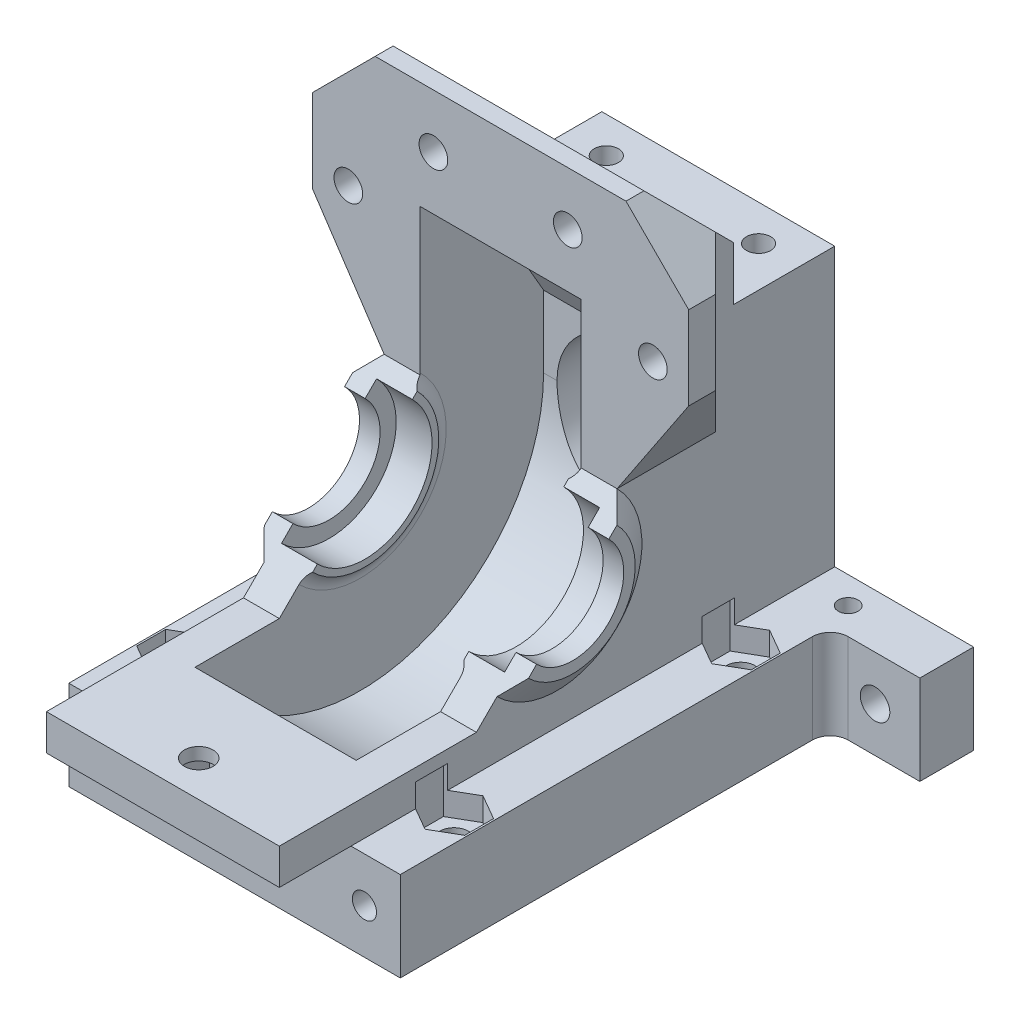
SolidWorks part; units mm, degrees
ref_plane "Plan de face" through (0, 0, 0) normal (0, 0, 1) x (1, 0, 0)
ref_plane "Plan de dessus" through (0, 0, 0) normal (0, 1, 0) x (1, 0, 0)
ref_plane "Plan de droite" through (0, 0, 0) normal (1, 0, 0) x (0, 0, -1)
ref_plane "Plan1" through (0, -23, 0) normal (0, 1, 0) x (1, 0, 0)
sketch "Esquisse1" plane through (0, -23, 0) normal (0, 1, 0) x (1, 0, 0)
  line L0 (0, 36.285) -> (0, -30.3608) construction
  line L1 (18.5, -23) -> (-18.5, -23)
  line L2 (-18.5, -23) -> (-18.5, 25)
  line L3 (-18.5, 25) -> (-28.5, 25)
  line L4 (-28.5, 25) -> (-28.5, 31)
  line L5 (-28.5, 31) -> (28.5, 31)
  line L6 (28.5, 25) -> (28.5, 31)
  line L7 (18.5, 25) -> (28.5, 25)
  line L8 (18.5, -23) -> (18.5, 25)
  circle A0 centre (-17.5, 28) radius 1.1
  circle A1 centre (-15.5, 18) radius 1.6
  circle A2 centre (-15.5, -14) radius 1.6
  circle A3 centre (15.5, -14) radius 1.6
  circle A4 centre (15.5, 18) radius 1.6
  circle A5 centre (17.5, 28) radius 1.1
  point P15 (-28.5, 28)
  point P23 (0, 31)
  point P26 (0, -23)
  dimension "D1" = 3.2
  dimension "D2" = 2.2
  dimension "D3" = 54
  dimension "D4" = 37
  dimension "D5" = 57
  dimension "D6" = 6
  dimension "D7" = 23
  dimension "D8" = 32
  dimension "D9" = 9
  dimension "D10" = 15.5
  dimension "D11" = 17.5
extrude "Boss.-Extru.1" add sketch "Esquisse1" along normal blind 10
sketch "Esquisse2" plane through (0, 0, 0) normal (1, 0, 0) x (0, 0, -1)
  line L0 (31, -13) -> (-31, -13)
  line L1 (-31, -13) -> (-31, -9)
  line L2 (-31, -9) -> (-9, -9)
  line L3 (-9, -9) -> (-4.0305, -4.0305)
  line L4 (6.7, 6.7) -> (6.7, 35)
  line L5 (6.7, 35) -> (8.7, 35)
  line L6 (8.7, 35) -> (19.7, 24)
  line L7 (19.7, 24) -> (19.7, 18)
  line L8 (19.7, 18) -> (31, 18)
  line L9 (31, 18) -> (31, -13)
  line L10 (4.0305, 4.0305) -> (6.7, 6.7)
  line L11 (-23, -23) -> (25, -23) construction
  arc A0 (-4.0305, -4.0305) -> (4.0305, 4.0305) centre (0, 0) ccw
  dimension "D3" = 5.7
  dimension "D1" = 62
  dimension "D2" = 45
  dimension "D4" = 4
  dimension "D5" = 31
  dimension "D6" = 58
  dimension "D7" = 11.3
  dimension "D8" = 2
  dimension "D9" = 45
  dimension "D10" = 6.7
extrude "Boss.-Extru.2" add sketch "Esquisse2" along normal blind 13 and the other way blind 13
ref_axis "Axe1" through (-21.0876, 0, 0) along (1, 0, 0)
sketch "Esquisse3" plane through (13, 0, 0) normal (1, 0, 0) x (0, 0, -1)
  line L0 (-4.0305, -4.0305) -> (-9, -9) construction
  line L1 (-6.7, -6.7) -> (-4.0305, -4.0305)
  line L2 (6.7, 6.7) -> (4.0305, 4.0305)
  arc A0 (6.7, 6.7) -> (-6.7, -6.7) centre (0, 0) cw
  arc A1 (4.0305, 4.0305) -> (-4.0305, -4.0305) centre (0, 0) cw
  arc A2 (-4.0305, -4.0305) -> (4.0305, 4.0305) centre (0, 0) ccw construction
extrude "Boss.-Extru.3" add sketch "Esquisse3" along direction (1, 0, 0) on the side of the normal blind 1.75
sketch "Esquisse4" plane through (19.7, 0, -6.7) normal (0, 0, -1) x (-1, 0, 0)
  line L1 (6.7, 6.7) -> (-1.3, 18.7)
  line L2 (6.7, 6.7) -> (6.7, 26)
  line L3 (6.7, 26) -> (-1.3, 26)
  line L4 (-1.3, 18.7) -> (-1.3, 26)
  line L5 (19.7, -1.2226) -> (19.7, 36.1601) construction
  line L6 (40.7, 18.7) -> (40.7, 26)
  line L7 (32.7, 26) -> (40.7, 26)
  line L8 (32.7, 6.7) -> (32.7, 26)
  line L9 (32.7, 6.7) -> (40.7, 18.7)
  dimension "D1" = 8
  dimension "D2" = 7.3
  dimension "D3" = 19.3
extrude "Boss.-Extru.7" add sketch "Esquisse4" along normal blind 11
chamfer "Chanfrein2" distance 8 angle 45 2 edges at (-21, 22.35, -17.7) (21, 22.35, -17.7)
sketch "Esquisse6" plane through (0, 0, 23) normal (0, 0, 1) x (1, 0, 0)
  line L0 (-21.0876, 0) -> (21.3474, 0) construction
  line L1 (0, -25.736) -> (0, 38.7997) construction
  line L4 (28.5, -13) -> (28.5, -23) construction
  line L5 (18.5, -13) -> (28.5, -13) construction
  circle A0 centre (17, 21) radius 1.6
  circle A1 centre (7.5, 29) radius 1.6
  circle A2 centre (23.5, -18) radius 1.65
  point P13 (28.5, -18)
  point P16 (23.5, -13)
  dimension "D1" = 3.2
  dimension "D6" = 3.3
  dimension "D2" = 21
  dimension "D3" = 29
  dimension "D4" = 7.5
  dimension "D5" = 17
extrude "Enlèv. mat.-Extru.3" cut sketch "Esquisse6" against normal blind 52
sketch "Esquisse7" plane through (0, 0, -31) normal (0, 0, -1) x (-1, 0, 0)
  line L0 (-21, 18.7) -> (-21, 26) construction
  line L1 (-14.2, 22.6166) -> (-17, 24.2332)
  line L2 (-17, 24.2332) -> (-19.8, 22.6166)
  line L3 (-19.8, 22.6166) -> (-19.8, 19.3834)
  line L4 (-19.8, 19.3834) -> (-17, 17.7668)
  line L5 (-17, 17.7668) -> (-14.2, 19.3834)
  line L6 (-14.2, 19.3834) -> (-14.2, 22.6166)
  line L7 (-4.2668, 29) -> (-5.8834, 31.8)
  line L8 (-5.8834, 31.8) -> (-9.1166, 31.8)
  line L9 (-9.1166, 31.8) -> (-10.7332, 29)
  line L10 (-10.7332, 29) -> (-9.1166, 26.2)
  line L11 (-9.1166, 26.2) -> (-5.8834, 26.2)
  line L12 (-5.8834, 26.2) -> (-4.2668, 29)
  line L14 (13, 35) -> (-13, 35) construction
  circle A0 centre (-17, 21) radius 2.8 construction
  circle A1 centre (-7.5, 29) radius 2.8 construction
  dimension "D1" = 5.6
extrude "Enlèv. mat.-Extru.17" cut sketch "Esquisse7" against normal up to vertex (21.3 mm away) up to point (21, 18.7, -9.7)
sketch "Esquisse31" plane through (0, 0, 23) normal (0, 0, 1) x (1, 0, 0)
  line L0 (18.5, -13) -> (18.5, -23) construction
  line L1 (0, -26.7777) -> (0, -12.003) construction
  circle A0 centre (14.5, -18) radius 1.35
  circle A1 centre (-14.5, -18) radius 1.35
  point P7 (18.5, -18)
  dimension "D1" = 2.7
  dimension "D2" = 29
extrude "Enlèv. mat.-Extru.16" cut sketch "Esquisse31" against normal blind 10
sketch "Esquisse9" plane through (0, -13, 0) normal (0, 1, 0) x (1, 0, 0)
  line L1 (18.3, -15.6166) -> (18.3, -12.3834)
  line L2 (18.3, -12.3834) -> (15.5, -10.7668)
  line L3 (15.5, -10.7668) -> (12.7, -12.3834)
  line L4 (12.7, -12.3834) -> (12.7, -15.6166)
  line L5 (12.7, -15.6166) -> (15.5, -17.2332)
  line L6 (15.5, -17.2332) -> (18.3, -15.6166)
  line L7 (18.3, 19.6166) -> (15.5, 21.2332)
  line L8 (15.5, 21.2332) -> (12.7, 19.6166)
  line L9 (12.7, 19.6166) -> (12.7, 16.3834)
  line L10 (12.7, 16.3834) -> (15.5, 14.7668)
  line L11 (15.5, 14.7668) -> (18.3, 16.3834)
  line L12 (18.3, 16.3834) -> (18.3, 19.6166)
  line L13 (18.5, -23) -> (18.5, 25) construction
  circle A0 centre (15.5, -14) radius 2.8 construction
  circle A1 centre (15.5, 18) radius 2.8 construction
  dimension "D1" = 5.6
extrude "Enlèv. mat.-Extru.5" cut sketch "Esquisse9" against normal blind 2.6 and the other way blind 2.6
sketch "Esquisse13" plane through (0, 18, 0) normal (0, 1, 0) x (1, 0, 0)
  line L0 (-13, 19.7) -> (13, 19.7) construction
  line L2 (0, -31.9) -> (0, 31.9) construction
  circle A0 centre (8.5, 27) radius 1.35
  dimension "D1" = 2.7
  dimension "D2" = 8.5
  dimension "D3" = 7.3
extrude "Enlèv. mat.-Extru.6" cut sketch "Esquisse13" against normal blind 8
sketch "Esquisse14" plane through (0, 0, 0) normal (1, 0, 0) x (0, 0, -1)
  line L0 (-9, -9) -> (-31, -9) construction
  line L1 (20.5, 0) -> (20.5, 8)
  line L2 (20.5, 8) -> (13.5718, 20)
  line L3 (13.5718, 20) -> (6.7, 23)
  line L4 (6.7, 35) -> (6.7, 26) construction
  line L5 (-4.0305, -4.0305) -> (-9, -9) construction
  line L7 (-9, -9) -> (-18.4187, -9)
  line L8 (-4.0305, -4.0305) -> (-9, -9)
  line L9 (6.7, 6.7) -> (4.0305, 4.0305)
  line L10 (6.7, 23) -> (6.7, 6.7)
  arc A0 (20.5, 0) -> (-18.4187, -9) centre (0, 0) cw
  arc A1 (-4.0305, -4.0305) -> (4.0305, 4.0305) centre (0, 0) ccw construction
  arc A2 (-4.0305, -4.0305) -> (4.0305, 4.0305) centre (0, 0) ccw
  dimension "D1" = 20.5
  dimension "D2" = 8
  dimension "D3" = 12
  dimension "D4" = 150
  dimension "D5" = 23
extrude "Enlèv. mat.-Extru.7" cut sketch "Esquisse14" against normal blind 9 and the other way blind 9
ref_plane "Plan3" through (8.45, 0, 0) normal (1, 0, 0) x (0, 0, -1)
sketch "Esquisse17" plane through (8.45, 0, 0) normal (1, 0, 0) x (0, 0, -1)
  line L0 (-4.0305, -4.0305) -> (-9, -9) construction
  line L1 (4.0305, 4.0305) -> (5.8336, 5.8336)
  line L2 (-4.0305, -4.0305) -> (-5.8336, -5.8336)
  arc A0 (5.8336, 5.8336) -> (-5.8336, -5.8336) centre (0, 0) cw
  arc A2 (4.0305, 4.0305) -> (-4.0305, -4.0305) centre (0, 0) cw
  dimension "D1" = 2.55
extrude "Boss.-Extru.5" add sketch "Esquisse17" along normal up to next
sketch "Esquisse18" plane through (8.45, 0, 0) normal (-1, 0, 0) x (0, 0, 1)
  line L0 (-5.8336, 5.8336) -> (-4.0305, 4.0305) construction
  line L1 (-5.3033, 5.3033) -> (5.3033, -5.3033)
  arc A0 (-5.3033, 5.3033) -> (5.3033, -5.3033) centre (0, 0) ccw
  dimension "D1" = 7.5
extrude "Enlèv. mat.-Extru.8" cut sketch "Esquisse18" against normal blind 4
mirror "Symétrie1" about plane through (0, 0, 0) normal (1, 0, 0) of "Enlèv. mat.-Extru.16", "Enlèv. mat.-Extru.8", "Enlèv. mat.-Extru.6", "Enlèv. mat.-Extru.5", "Enlèv. mat.-Extru.3", "Boss.-Extru.3", "Boss.-Extru.5", "Enlèv. mat.-Extru.17"
fillet "Congé1" radius 2 4 edges at (9, -5.8336, -5.8336) (-9, -5.8336, -5.8336) (18.5, -18, -25) (-18.5, -18, -25)
sketch "Esquisse21" plane through (0, -13, 0) normal (0, -1, 0) x (1, 0, 0)
  line L0 (0, -31.9) -> (0, 31.9) construction
  circle A0 centre (0, 27) radius 1.6
  dimension "D1" = 3.2
extrude "Enlèv. mat.-Extru.10" cut sketch "Esquisse21" against normal up to next
sketch "Esquisse22" plane through (0, -13, 0) normal (0, -1, 0) x (1, 0, 0)
  line L0 (-13, 31) -> (13, 31) construction
  line L1 (3.2332, 27) -> (1.6166, 29.8)
  line L2 (1.6166, 29.8) -> (-1.6166, 29.8)
  line L3 (-1.6166, 29.8) -> (-3.2332, 27)
  line L4 (-3.2332, 27) -> (-1.6166, 24.2)
  line L5 (-1.6166, 24.2) -> (1.6166, 24.2)
  line L6 (1.6166, 24.2) -> (3.2332, 27)
  circle A0 centre (0, 27) radius 2.8 construction
  dimension "D1" = 5.6
extrude "Enlèv. mat.-Extru.11" cut sketch "Esquisse22" against normal blind 2.6
sketch "Esquisse30" plane through (0, 0, -31) normal (0, 0, -1) x (-1, 0, 0)
  circle A0 centre (0, 0) radius 6
  circle A1 centre (0, 0) radius 3.5
  dimension "D1" = 12
extrude "Boss.-Extru.6" add sketch "Esquisse30" along normal blind 3.5
fillet "Congé2" radius 3.5 1 edges at (6, 0, -31)
sketch "Esquisse25" plane through (0, 0, -31) normal (0, 0, -1) x (-1, 0, 0)
  circle A0 centre (0, 0) radius 5.1
  dimension "D1" = 10.2
extrude "Enlèv. mat.-Extru.12" cut sketch "Esquisse25" against normal up to next and the other way blind 2.5
sketch "Esquisse26" plane through (0, 0, -20.5) normal (0, 0, 1) x (1, 0, 0)
  circle A0 centre (0, 0) radius 7.5
  arc A5 (5.1, 0) -> (-5.1, 0) centre (0, 0) ccw construction
  dimension "D1" = 15
extrude "Enlèv. mat.-Extru.13" cut sketch "Esquisse26" against normal blind 5 and the other way up to next
ref_axis "Axe2" through (0, 0, 13.8458) along (0, 0, -1)
chamfer "Chanfrein3" distance 1.75 distance2 2.5 1 edges at (14.75, -6.7, -6.7) first distance on face at (13.875, -3.35, -3.35)
chamfer "Chanfrein4" distance 2.5 distance2 1.75 1 edges at (-14.75, -6.7, -6.7) first distance on face at (-14.75, -2.6826, -2.6826)
chamfer "Chanfrein5" distance 10 angle 45 2 edges at (13, 26, -12.2) (-13, 26, -12.2)
ref_axis "Axe3" through (8.5, 10, -27) along (0, 1, 0)
